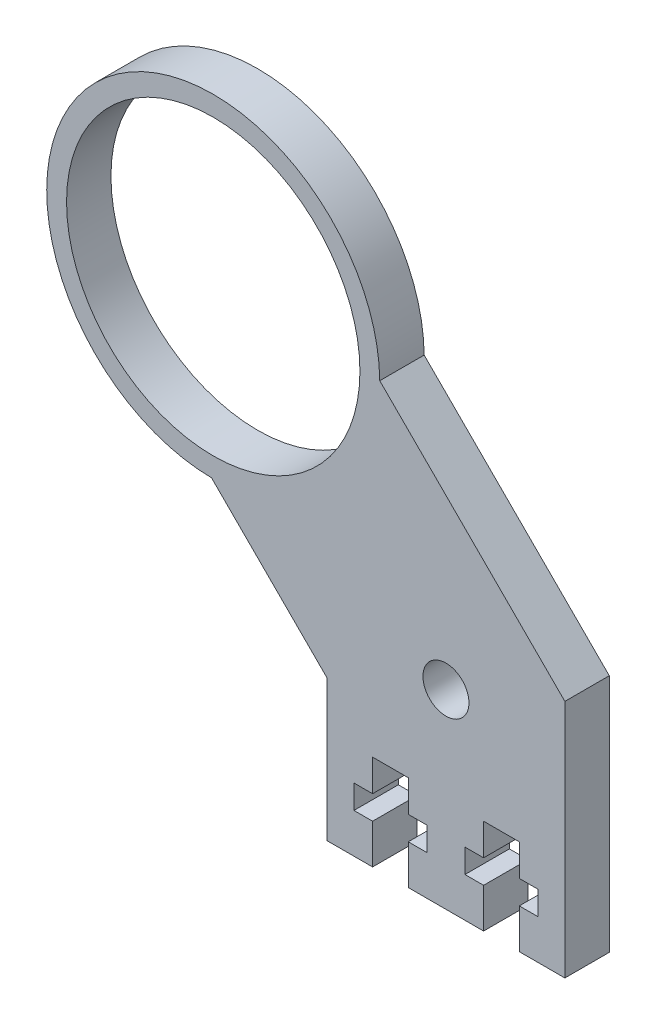
SolidWorks part; units mm, degrees
ref_plane "Front Plane" through (0, 0, 0) normal (0, 0, 1) x (1, 0, 0)
ref_plane "Top Plane" through (0, 0, 0) normal (0, 1, 0) x (1, 0, 0)
ref_plane "Right Plane" through (0, 0, 0) normal (1, 0, 0) x (0, 0, -1)
sketch "Sketch1" plane through (0, 0, 0) normal (0, 0, 1) x (1, 0, 0)
  line L0 (0, 0) -> (-29.3449, 29.3449) construction
  line L1 (0, 0) -> (0, 31.0325) construction
  line L2 (-15, -6.2132) -> (-15, -24)
  line L3 (-15, -24) -> (15, -24)
  line L4 (15, -24) -> (15, 6.2132)
  line L5 (0, 0) -> (0, -24) construction
  line L6 (15, 6.2132) -> (-8.346, 29.5592)
  line L7 (-15, -6.2132) -> (-29.5592, 8.346)
  line L8 (10.6066, 10.6066) -> (-18.7383, 39.9515) construction
  line L9 (-10.6066, -10.6066) -> (-39.9515, 18.7383) construction
  circle A0 centre (0, 0) radius 2.9
  arc A1 (-8.346, 29.5592) -> (-29.5592, 8.346) centre (-29.3449, 29.3449) ccw
  dimension "D1" = 5.8
  dimension "D3" = 42
  dimension "D2" = 41.5
  dimension "D4" = 45
  dimension "D5" = 24
  dimension "D6" = 30
  dimension "D7" = 15
  dimension "D8" = 15
extrude "Boss-Extrude1" add sketch "Sketch1" along normal blind 5.6
sketch "Sketch2" plane through (0, 0, 5.6) normal (0, 0, 1) x (1, 0, 0)
  circle A0 centre (-29.3449, 29.3449) radius 18.5
  dimension "D1" = 37
extrude "Cut-Extrude1" cut sketch "Sketch2" against normal through all
sketch "Sketch3" plane through (0, 0, 5.6) normal (0, 0, 1) x (1, 0, 0)
  line L0 (-15, -24) -> (15, -24) construction
  line L1 (-9.25, -24) -> (-4.75, -24)
  line L2 (-9.25, -24) -> (-9.25, -19)
  line L3 (-9.25, -12) -> (-4.75, -12)
  line L4 (-4.75, -24) -> (-4.75, -19)
  line L5 (0, 0) -> (0, -24) construction
  line L6 (-4.75, -16) -> (-2.4, -16)
  line L7 (-11.6, -16) -> (-9.25, -16)
  line L8 (-11.6, -16) -> (-11.6, -19)
  line L9 (-11.6, -19) -> (-9.25, -19)
  line L10 (-2.4, -16) -> (-2.4, -19)
  line L11 (-9.25, -16) -> (-9.25, -12)
  line L12 (-4.75, -19) -> (-2.4, -19)
  line L13 (-4.75, -16) -> (-4.75, -12)
  line L14 (4.75, -16) -> (4.75, -12)
  line L15 (4.75, -19) -> (2.4, -19)
  line L16 (9.25, -16) -> (9.25, -12)
  line L17 (2.4, -16) -> (2.4, -19)
  line L18 (11.6, -19) -> (9.25, -19)
  line L19 (11.6, -16) -> (11.6, -19)
  line L20 (11.6, -16) -> (9.25, -16)
  line L21 (4.75, -16) -> (2.4, -16)
  line L22 (4.75, -24) -> (4.75, -19)
  line L23 (9.25, -12) -> (4.75, -12)
  line L24 (9.25, -24) -> (9.25, -19)
  line L25 (9.25, -24) -> (4.75, -24)
  point P6 (-7, -12)
  point P18 (-10.425, -19)
  dimension "D1" = 4.5
  dimension "D2" = 7
  dimension "D3" = 12
  dimension "D4" = 9.2
  dimension "D5" = 3
  dimension "D6" = 5
extrude "Cut-Extrude2" cut sketch "Sketch3" against normal through all
equation "\"smallPulleyTeeth\"= 15"
equation "\"largePulleyTeeth\"= 30"
equation "\"eighthThick\"= 2.9mm"
equation "\"sixteenthThick\" = 1.7mm"
equation "\"wheelEighthThick\"=3.0mm"
equation "\"quarterThick\"=5.6mm"
equation "\"OD\" = 150mm"
equation "\"puckAngle\" = 60.5deg"
equation "\"puckDiam\" = 76.5mm"
equation "\"axlePress\" = 5.8mm"
equation "\"D1@Sketch1\"=\"axlePress\""
equation "\"D1@Boss-Extrude1\"=\"quarterThick\""
equation "\"press\" = 0.3mm"
equation "\"wheelClear\" = 0.3mm"
equation "\"10-32clear\" = 4.5mm"
equation "\"D1@Sketch3\"=\"10-32clear\""
